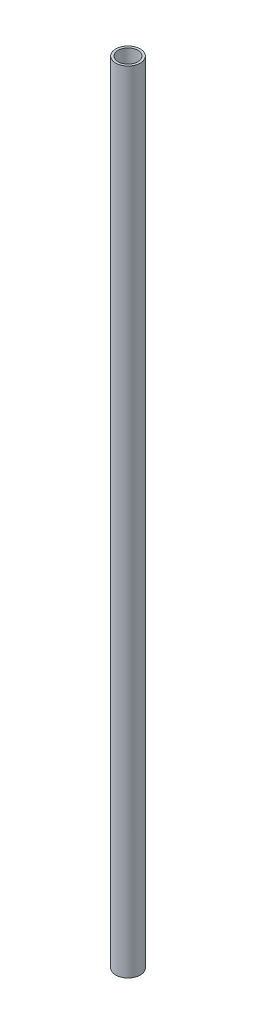
SolidWorks part; units mm, degrees
ref_plane "Front Plane" through (0, 0, 0) normal (0, 0, 1) x (1, 0, 0)
ref_plane "Top Plane" through (0, 0, 0) normal (0, 1, 0) x (1, 0, 0)
ref_plane "Right Plane" through (0, 0, 0) normal (1, 0, 0) x (0, 0, -1)
sketch "Sketch1" plane through (0, 0, 0) normal (0, 1, 0) x (1, 0, 0)
  circle A0 centre (0, 0) radius 0.3977
  circle A1 centre (0, 0) radius 0.3215
  dimension "D1" = 0.643
  dimension "D2" = 0.0762
extrude "Boss-Extrude1" add sketch "Sketch1" along normal up to surface (25.57 mm away)
